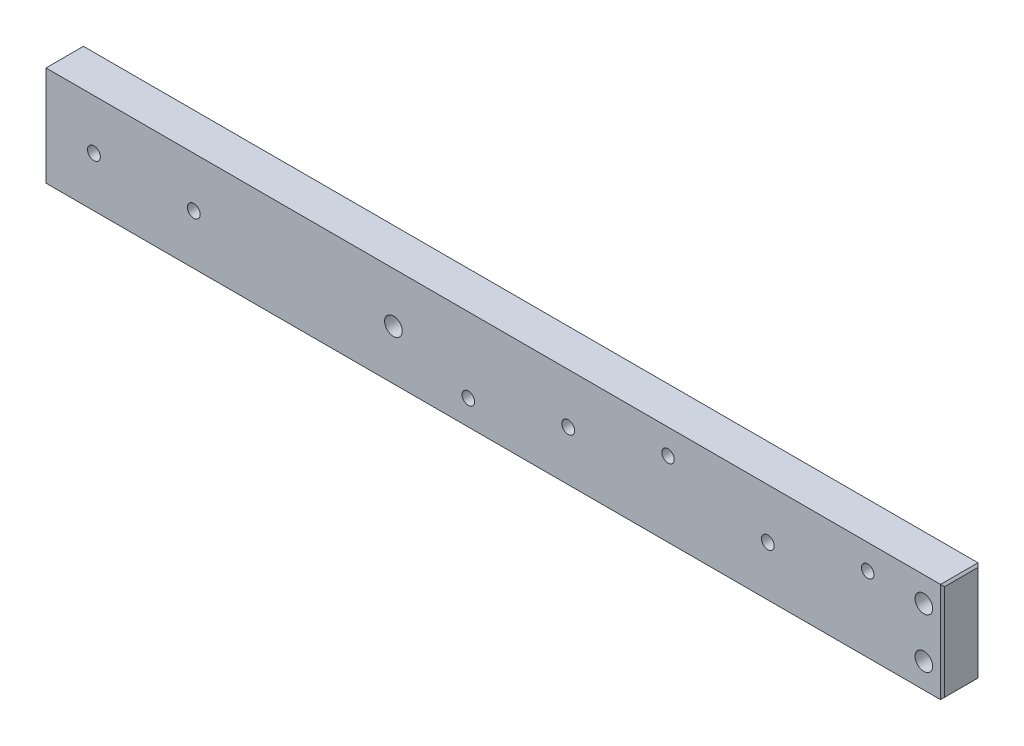
SolidWorks part; units mm, degrees
material "6061-T6 (SS)"
ref_plane "Front Plane" through (0, 0, 0) normal (0, 0, 1) x (1, 0, 0)
ref_plane "Top Plane" through (0, 0, 0) normal (0, 1, 0) x (1, 0, 0)
ref_plane "Right Plane" through (0, 0, 0) normal (1, 0, 0) x (0, 0, -1)
sketch "Sketch1" plane through (0, 0, 0) normal (0, 0, 1) x (1, 0, 0)
  line L1 (0, 0) -> (-228.6, 0)
  line L2 (0, 0) -> (0, 25.4)
  line L3 (0, 25.4) -> (-228.6, 25.4)
  line L4 (-228.6, 0) -> (-228.6, 25.4)
  dimension "D1" = 25.4
  dimension "D2" = 228.6
extrude "Boss-Extrude1" add sketch "Sketch1" along normal blind 9.525
sketch "Sketch2" plane through (0, 0, 9.525) normal (0, 0, 1) x (1, 0, 0)
  line L0 (-4.7625, 6.35) -> (-4.7625, 19.05)
  line L1 (-4.7625, 19.05) -> (-4.7625, 25.4)
  line L2 (0, 25.4) -> (-228.6, 25.4) construction
  line L3 (-4.7625, 6.35) -> (-4.7625, 0)
  line L4 (-228.6, 0) -> (0, 0) construction
  line L5 (0, 0) -> (0, 25.4) construction
  dimension "D1" = 4.7625
  dimension "D2" = 12.7
hole_wizard "#8 Clearance Hole1" positions "Sketch3" profile "Sketch4" hole size "#8" standard "ANSI Inch"
sketch "Sketch3" plane through (0, 0, 9.525) normal (0, 0, 1) x (1, 0, 0)
  point P0 (-4.7625, 6.35)
  point P3 (-4.7625, 19.05)
sketch "Sketch4" plane through (-4.7625, 6.35, 9.525) normal (1, 0, 0) x (0, -1, 0)
  line L0 (0, 0) -> (0, 26.7507)
  line L1 (0, 26.7507) -> (2.2479, 25.4)
  line L2 (2.2479, 25.4) -> (2.2479, 0)
  line L5 (2.2479, 0) -> (0, 0)
  line L10 (0, 26.7507) -> (-2.2479, 25.4) construction
  line L11 (0, -6.35) -> (0, 107.95) construction
  dimension "Hole Dia." = 4.4958
  dimension "Hole Depth" = 25.4
  dimension "Drill Angle" = 118
hole_wizard "#8 Clearance Hole2" positions "Sketch8" profile "Sketch9" hole size "#8" standard "ANSI Inch"
sketch "Sketch8" plane through (0, 0, 9.525) normal (0, 0, 1) x (1, 0, 0)
  line L0 (-203.2, 12.7) -> (-139.7, 12.7)
  line L1 (-203.2, 12.7) -> (-228.6, 12.7)
  line L2 (-228.6, 25.4) -> (-228.6, 0) construction
  point P2 (-139.7, 12.7)
  dimension "D1" = 63.5
  dimension "D2" = 25.4
sketch "Sketch9" plane through (-139.7, 12.7, 9.525) normal (1, 0, 0) x (0, -1, 0)
  line L0 (0, 0) -> (0, 20.4007)
  line L1 (0, 20.4007) -> (2.2479, 19.05)
  line L2 (2.2479, 19.05) -> (2.2479, 0)
  line L5 (2.2479, 0) -> (0, 0)
  line L10 (0, 20.4007) -> (-2.2479, 19.05) construction
  line L11 (0, -6.35) -> (0, 107.95) construction
  dimension "Hole Dia." = 4.4958
  dimension "Hole Depth" = 19.05
  dimension "Drill Angle" = 118
chamfer "Chamfer1" distance 0.508 angle 45 8 edges at (0, 0, 4.7625) (0, 12.7, 9.525) (0, 25.4, 4.7625) (0, 12.7, 0) (-228.6, 25.4, 4.7625) (-228.6, 12.7, 9.525) (-228.6, 0, 4.7625) (-228.6, 12.7, 0)
hole_wizard "#4 Clearance Hole1" positions "Sketch10" profile "Sketch12" hole size "#4" standard "ANSI Inch" end condition through all
sketch "Sketch10" plane through (0, 0, 0) normal (0, 0, -1) x (-1, 0, 0)
  point P0 (95.25, 12.7)
  point P3 (44.45, 12.7)
sketch "Sketch12" plane through (-95.25, 12.7, 0) normal (1, 0, 0) x (0, 1, 0)
  line L0 (0, 0) -> (0, 9.525)
  line L1 (0, 9.525) -> (1.6319, 9.525)
  line L2 (1.6319, 9.525) -> (1.6319, 0)
  line L5 (1.6319, 0) -> (0, 0)
  line L11 (0, -6.35) -> (0, 107.95) construction
  dimension "Thru Hole Dia." = 3.2639
  dimension "Thru Hole Depth" = 9.525
hole_wizard "#4 Clearance Hole2" positions "Sketch13" profile "Sketch14" hole size "#4" standard "ANSI Inch" end condition up to next
sketch "Sketch13" plane through (0, 0, 9.525) normal (0, 0, 1) x (1, 0, 0)
  line L0 (-215.9, 12.7) -> (-190.5, 12.7)
  line L2 (-228.092, 25.4) -> (-228.092, 0) construction
  line L3 (-139.7, 12.7) -> (-203.2, 12.7) construction
  point P0 (-215.9, 12.7)
  point P2 (-190.5, 12.7)
  point P11 (-228.092, 12.7)
  dimension "D1" = 25.4
  dimension "D2" = 63.5
sketch "Sketch14" plane through (-215.9, 12.7, 9.525) normal (1, 0, 0) x (0, -1, 0)
  line L0 (0, 0) -> (0, 9.525)
  line L1 (0, 9.525) -> (1.6319, 9.525)
  line L2 (1.6319, 9.525) -> (1.6319, 0)
  line L5 (1.6319, 0) -> (0, 0)
  line L11 (0, -6.35) -> (0, 107.95) construction
  dimension "Thru Hole Dia." = 3.2639
  dimension "Thru Hole Depth" = 9.525
hole_wizard "1/8 (0.125) Diameter Hole1" positions "Sketch15" profile "Sketch17" hole size "1/8" standard "ANSI Inch" end condition up to next
sketch "Sketch15" plane through (0, 0, 9.525) normal (0, 0, 1) x (1, 0, 0)
  line L1 (0, 24.892) -> (0, 0.508) construction
  line L2 (-69.85, 19.05) -> (-19.05, 19.05)
  line L5 (-0.508, 25.4) -> (-228.092, 25.4) construction
  line L6 (-228.092, 0) -> (-0.508, 0) construction
  point P0 (-19.05, 19.05)
  point P2 (-69.85, 19.05)
  point P22 (-120.65, 6.35)
  dimension "D1" = 69.85
  dimension "D2" = 19.05
  dimension "D3" = 6.35
  dimension "D4" = 6.35
  dimension "D5" = 120.65
sketch "Sketch17" plane through (-19.05, 19.05, 9.525) normal (1, 0, 0) x (0, -1, 0)
  line L0 (0, 0) -> (0, 9.525)
  line L1 (0, 9.525) -> (1.5875, 9.525)
  line L2 (1.5875, 9.525) -> (1.5875, 0)
  line L5 (1.5875, 0) -> (0, 0)
  line L11 (0, -6.35) -> (0, 107.95) construction
  dimension "Thru Hole Dia." = 3.175
  dimension "Thru Hole Depth" = 9.525
